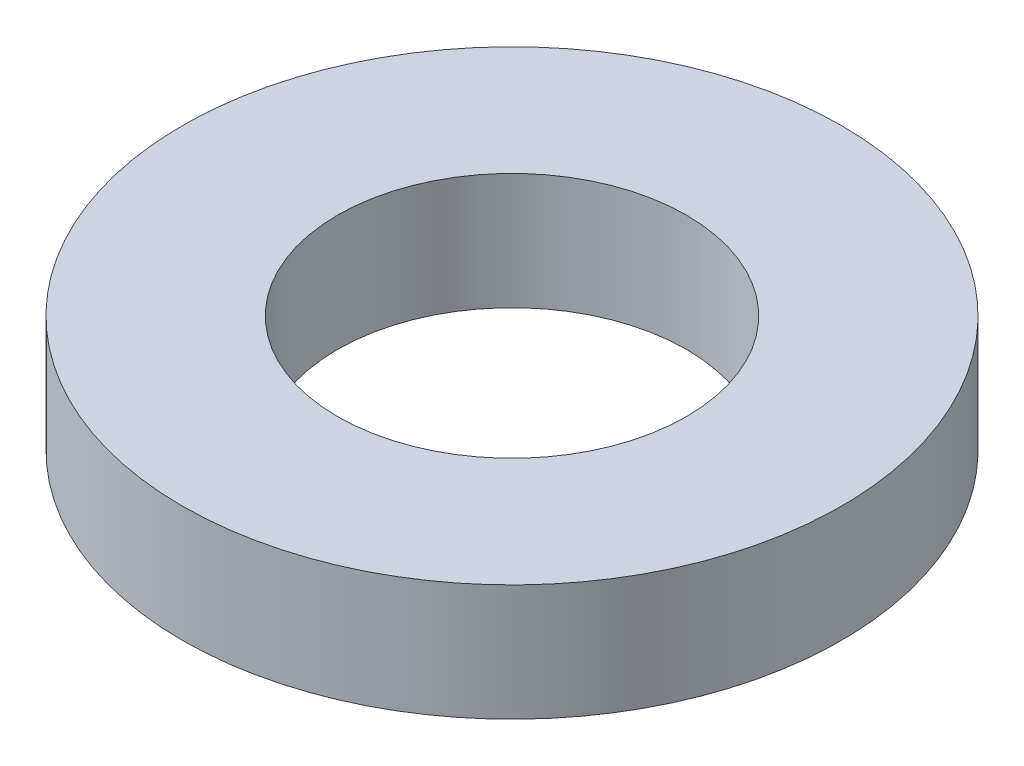
SolidWorks part; units mm, degrees
ref_plane "Front Plane" through (0, 0, 0) normal (0, 0, 1) x (1, 0, 0)
ref_plane "Top Plane" through (0, 0, 0) normal (0, 1, 0) x (1, 0, 0)
ref_plane "Right Plane" through (0, 0, 0) normal (1, 0, 0) x (0, 0, -1)
sketch "Sketch1" plane through (0, 0, 0) normal (0, 1, 0) x (1, 0, 0)
  circle A0 centre (0, 0) radius 85
  dimension "FLANGE_OD" = 170
extrude "Boss-Extrude1" add sketch "Sketch1" along normal blind 30
sketch "Sketch2" plane through (0, 0, 0) normal (0, 1, 0) x (1, 0, 0)
  circle A0 centre (0, 0) radius 45
  dimension "BORE_D" = 90
extrude "Cut-Extrude1" cut sketch "Sketch2" along normal through all
sketch "Sketch3" plane through (0, 30, 0) normal (0, 1, 0) x (1, 0, 0)
  circle A0 centre (0, 0) radius 34.801 construction
  circle A1 centre (-34.801, 0) radius 3.666
  dimension "BOLT_D" = 7.332
  dimension "BOLT_PCD" = 69.6019
extrude "Cut-Extrude2" cut sketch "Sketch3" against normal blind 25.116 rebuild error yes
pattern_circular "CirPattern1" count 5 over 360 rebuild error yes
